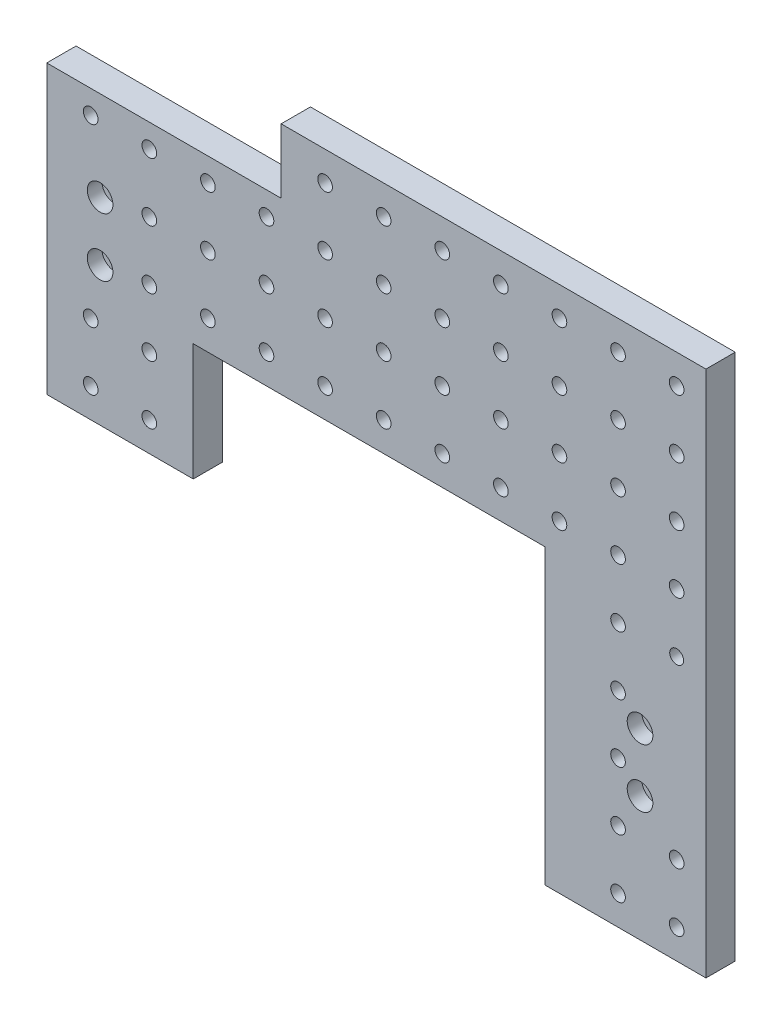
SolidWorks part; units mm, degrees
note: The reader was unsure of these and kept them because the rebuilt part matched: shared geometry of "Sketch6<3>", "Sketch6<4>", "Sketch8<3>".
ref_plane "Front Plane" through (0, 0, 0) normal (0, 0, 1) x (1, 0, 0)
ref_plane "Top Plane" through (0, 0, 0) normal (0, 1, 0) x (1, 0, 0)
ref_plane "Right Plane" through (0, 0, 0) normal (1, 0, 0) x (0, 0, -1)
sketch "Sketch1" plane through (0, 0, 0) normal (0, 0, 1) x (1, 0, 0)
  line L0 (0, 0) -> (63.5, 0)
  line L2 (82.55, 50.8) -> (215.9, 50.8)
  line L3 (215.9, 50.8) -> (215.9, -76.2)
  line L4 (215.9, -76.2) -> (285.75, -76.2)
  line L5 (285.75, -76.2) -> (285.75, 152.4)
  line L6 (285.75, 152.4) -> (0, 152.4)
  line L7 (0, 152.4) -> (0, 0)
  line L8 (63.5, 0) -> (63.5, 50.8)
  line L9 (63.5, 50.8) -> (82.55, 50.8)
  circle A1 centre (44.45, 12.7) radius 3.175
  circle A2 centre (44.45, 38.1) radius 3.175
  circle A3 centre (44.45, 63.5) radius 3.175
  circle A4 centre (44.45, 88.9) radius 3.175
  circle A5 centre (44.45, 114.3) radius 3.175
  circle A6 centre (44.45, 139.7) radius 3.175
  circle A8 centre (69.85, 63.5) radius 3.175
  circle A9 centre (69.85, 88.9) radius 3.175
  circle A10 centre (69.85, 114.3) radius 3.175
  circle A11 centre (69.85, 139.7) radius 3.175
  circle A12 centre (95.25, 139.7) radius 3.175
  circle A13 centre (120.65, 139.7) radius 3.175
  circle A14 centre (146.05, 139.7) radius 3.175
  circle A15 centre (171.45, 139.7) radius 3.175
  circle A16 centre (196.85, 139.7) radius 3.175
  circle A17 centre (222.25, 139.7) radius 3.175
  circle A18 centre (247.65, 139.7) radius 3.175
  circle A19 centre (273.05, 139.7) radius 3.175
  circle A20 centre (95.25, 114.3) radius 3.175
  circle A21 centre (120.65, 114.3) radius 3.175
  circle A22 centre (146.05, 114.3) radius 3.175
  circle A23 centre (171.45, 114.3) radius 3.175
  circle A24 centre (196.85, 114.3) radius 3.175
  circle A25 centre (222.25, 114.3) radius 3.175
  circle A26 centre (247.65, 114.3) radius 3.175
  circle A27 centre (273.05, 114.3) radius 3.175
  circle A28 centre (95.25, 88.9) radius 3.175
  circle A29 centre (120.65, 88.9) radius 3.175
  circle A30 centre (146.05, 88.9) radius 3.175
  circle A31 centre (171.45, 88.9) radius 3.175
  circle A32 centre (196.85, 88.9) radius 3.175
  circle A33 centre (222.25, 88.9) radius 3.175
  circle A34 centre (247.65, 88.9) radius 3.175
  circle A35 centre (273.05, 88.9) radius 3.175
  circle A36 centre (95.25, 63.5) radius 3.175
  circle A37 centre (120.65, 63.5) radius 3.175
  circle A38 centre (146.05, 63.5) radius 3.175
  circle A39 centre (171.45, 63.5) radius 3.175
  circle A40 centre (196.85, 63.5) radius 3.175
  circle A41 centre (222.25, 63.5) radius 3.175
  circle A42 centre (247.65, 63.5) radius 3.175
  circle A43 centre (273.05, 63.5) radius 3.175
  circle A44 centre (69.85, 114.3) radius 3.175
  circle A45 centre (69.85, 88.9) radius 3.175
  circle A46 centre (69.85, 63.5) radius 3.175
  circle A47 centre (247.65, 38.1) radius 3.175
  circle A48 centre (247.65, 12.7) radius 3.175
  circle A50 centre (247.65, -38.1) radius 3.175
  circle A55 centre (273.05, -38.1) radius 3.175
  circle A57 centre (247.65, -12.7) radius 3.175 [skipped]
  circle A58 centre (273.05, -12.7) radius 3.175 [skipped]
  circle A59 centre (247.65, -63.5) radius 3.175 [skipped]
  circle A60 centre (273.05, -63.5) radius 3.175 [skipped]
  circle A61 centre (273.05, 38.1) radius 3.175 [skipped]
  circle A62 centre (19.05, 139.7) radius 3.175
  circle A63 centre (19.05, 114.3) radius 3.175
  circle A67 centre (19.05, 12.7) radius 3.175
  circle A68 centre (273.05, -38.1) radius 3.175
  circle A69 centre (273.05, -63.5) radius 3.175
  circle A70 centre (247.65, -63.5) radius 3.175
  circle A71 centre (19.05, 38.1) radius 3.175 [skipped]
  circle A72 centre (19.05, 88.9) radius 3.175 [skipped]
  circle A73 centre (273.05, 38.1) radius 3.0017
  circle A74 centre (247.65, -12.7) radius 3.175
  circle A76 centre (273.05, 12.7) radius 3.175 [skipped]
  circle A78 centre (19.05, 38.1) radius 3.175
  circle A79 centre (19.05, 63.5) radius 3.175 [skipped]
  dimension "D7" = 63.5
  dimension "D17" = 6.35
  dimension "D19" = 6.35
  dimension "D2" = 2
  dimension "D3" = 69.85
  dimension "D4" = 228.6
  dimension "D5" = 101.6
  dimension "D6" = 152.4
  dimension "D8" = 2
  dimension "D9" = 25.4
  dimension "D16" = 25.4
  dimension "D10" = 152.4
  dimension "D12" = 9
  dimension "D13" = 4
  dimension "D14" = 6
  dimension "D15" = 6
  dimension "D18" = 6
extrude "Boss-Extrude1" add sketch "Sketch1" along normal blind 12.7
sketch "Sketch6" plane through (0, 0, 12.7) normal (0, 0, 1) x (1, 0, 0)
  line L0 (23.114, 54.591) -> (23.114, 60.1472)
  line L2 (23.114, 60.1472) -> (0, 60.1472)
  line L3 (0, 152.4) -> (0, 0) construction
  line L4 (285.75, 152.4) -> (0, 152.4) construction
  circle A0 centre (23.114, 60.1472) radius 3.3734
  circle A1 centre (23.114, 60.1472) radius 5.5563
  circle A2 centre (23.114, 85.5472) radius 3.3734
  circle A3 centre (23.114, 85.5472) radius 5.5562
  dimension "D3" = 6.7469
  dimension "D4" = 11.1125
  dimension "D6" = 11.1125
  dimension "D7" = 6.7469
  dimension "D1" = 23.114
  dimension "D2" = 66.8528
  dimension "D5" = 25.4
  dimension "D8" = 23.114
extrude "Cut-Extrude6" cut sketch "Sketch6" against normal blind 12.7 contours A2 | A0
extrude "Cut-Extrude7" cut sketch "Sketch6<3>" against normal blind 6.35 contours A3 A2 | L0 A1 L2 A0
sketch "Sketch6<3>" plane through (0, 0, 12.7) normal (0, 0, 1) x (1, 0, 0) same geometry as "Sketch6"
extrude "Cut-Extrude8" cut sketch "Sketch6<4>" against normal blind 6.35 contours L2 A1 L0 A0
sketch "Sketch6<4>" plane through (0, 0, 12.7) normal (0, 0, 1) x (1, 0, 0) same geometry as "Sketch6"
sketch "Sketch7" plane through (0, 0, 12.7) normal (0, 0, 1) x (1, 0, 0)
  line L1 (0, 152.4) -> (101.6, 152.4)
  line L2 (0, 152.4) -> (0, 124.46)
  line L3 (0, 124.46) -> (101.6, 124.46)
  line L4 (101.6, 152.4) -> (101.6, 124.46)
  dimension "D1" = 27.94
  dimension "D2" = 101.6
extrude "Cut-Extrude9" cut sketch "Sketch7" against normal blind 12.7
sketch "Sketch8" plane through (0, 0, 12.7) normal (0, 0, 1) x (1, 0, 0)
  line L0 (215.9, -76.2) -> (285.75, -76.2) construction
  line L2 (285.75, -76.2) -> (285.75, 152.4) construction
  circle A0 centre (257.175, -22.1742) radius 3.3734
  circle A1 centre (257.175, 3.2258) radius 3.3734
  circle A2 centre (257.175, 3.2258) radius 5.5562
  circle A3 centre (257.175, -22.1742) radius 5.5562
  dimension "D3" = 6.7469
  dimension "D5" = 11.1125
  dimension "D1" = 54.0258
  dimension "D2" = 25.4
  dimension "D4" = 28.575
extrude "Cut-Extrude10" cut sketch "Sketch8" against normal blind 12.7 contours A0 | A1
extrude "Cut-Extrude11" cut sketch "Sketch8<3>" against normal blind 6.35 from surface at 0 contours A2 A1 | A3 A0 starting at face at (260.5484, -22.1742, 12.7)
sketch "Sketch8<3>" plane through (0, 0, 12.7) normal (0, 0, 1) x (1, 0, 0) same geometry as "Sketch8"
